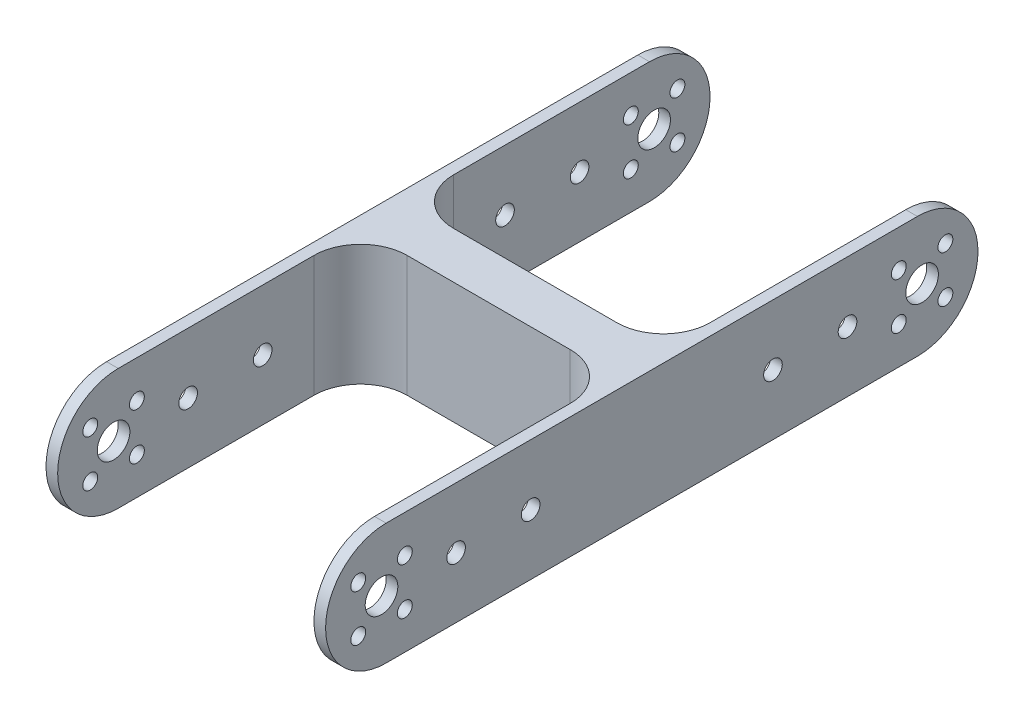
SolidWorks part; units mm, degrees
ref_plane "前视基准面" through (0, 0, 0) normal (0, 0, 1) x (1, 0, 0)
ref_plane "上视基准面" through (0, 0, 0) normal (0, 1, 0) x (1, 0, 0)
ref_plane "右视基准面" through (0, 0, 0) normal (1, 0, 0) x (0, 0, -1)
other "Configuration Table"
sketch "草图1" plane through (0, 0, 0) normal (0, 1, 0) x (1, 0, 0)
  line L0 (0, 0) -> (0, 140)
  line L1 (0, 140) -> (5, 140)
  line L2 (5, 140) -> (5, 85)
  line L3 (15, 75) -> (45, 75)
  line L4 (55, 85) -> (55, 140)
  line L5 (55, 140) -> (60, 140)
  line L6 (60, 140) -> (60, 0)
  line L7 (60, 0) -> (55, 0)
  line L8 (55, 0) -> (55, 55)
  line L9 (45, 65) -> (15, 65)
  line L10 (5, 55) -> (5, 0)
  line L11 (5, 0) -> (0, 0)
  arc A0 (55, 55) -> (45, 65) centre (45, 55) ccw
  arc A1 (5, 55) -> (15, 65) centre (15, 55) cw
  arc A2 (45, 75) -> (55, 85) centre (45, 85) ccw
  arc A3 (15, 75) -> (5, 85) centre (15, 85) cw
  point P3 (2.5, 140)
  point P16 (55, 65)
  point P19 (5, 65)
  point P22 (55, 75)
  point P25 (5, 75)
  dimension "D10" = 10
  dimension "D1" = 140
  dimension "D2" = 140
  dimension "D3" = 5
  dimension "D4" = 5
  dimension "D5" = 50
  dimension "D6" = 50
  dimension "D7" = 5
  dimension "D8" = 10
  dimension "D9" = 65
extrude "凸台-拉伸1" add sketch "草图1" along normal blind 26
sketch "草图2" plane through (60, 0, 0) normal (1, 0, 0) x (0, 0, -1)
  line L0 (-1000, 13) -> (49000, 13) construction
  line L1 (0, 26) -> (0, 0) construction
  line L2 (70, -974) -> (70, 49026) construction
  line L3 (0, 26) -> (140, 26) construction
  line L4 (0, 13) -> (12, 13)
  line L5 (12, 13) -> (28, 13)
  line L6 (7, 8) -> (17, 8)
  line L7 (7, 8) -> (7, 18)
  line L8 (7, 18) -> (17, 18)
  line L9 (17, 8) -> (17, 18)
  line L10 (7, 8) -> (17, 18) construction
  line L11 (7, 18) -> (17, 8) construction
  line L12 (28, 13) -> (44, 13)
  circle A0 centre (12, 13) radius 3.5
  circle A1 centre (7, 18) radius 1.6
  circle A2 centre (17, 18) radius 1.6
  circle A3 centre (17, 8) radius 1.6
  circle A4 centre (7, 8) radius 1.6
  circle A5 centre (28, 13) radius 2
  circle A6 centre (44, 13) radius 2
  circle A7 centre (96, 13) radius 2
  circle A8 centre (112, 13) radius 2
  circle A9 centre (123, 18) radius 1.6
  circle A10 centre (133, 18) radius 1.6
  circle A11 centre (133, 8) radius 1.6
  circle A12 centre (128, 13) radius 3.5
  circle A13 centre (123, 8) radius 1.6
  point P5 (0, 13)
  point P10 (70, 26)
  dimension "D2" = 7
  dimension "D5" = 3.2
  dimension "D8" = 4
  dimension "D10" = 4
  dimension "D1" = 12
  dimension "D3" = 10
  dimension "D4" = 10
  dimension "D7" = 16
  dimension "D9" = 16
  dimension "D6" = 4
extrude "切除-拉伸2" cut sketch "草图2" against normal through all contours A12 | A9 | A10 | A11 | A13 | A0 | A1 | A4 | A3 | A2 | A5 | A6 | A7 | A8 region at (60, 18, -123) region at (60, 18, -133) region at (60, 8, -133) region at (60, 13, -128) region at (60, 8, -123)
sketch "草图3" plane through (0, 0, 0) normal (-1, 0, 0) x (0, 0, 1)
  line L0 (-128, 13) -> (-127, 13)
  line L1 (-70, -974) -> (-70, 49026) construction
  line L2 (-140, 26) -> (-127, 26)
  line L3 (-140, 26) -> (-140, 0)
  line L4 (-140, 0) -> (-127, 0)
  line L5 (-127, 26) -> (-127, 0)
  line L6 (-140, 26) -> (0, 26) construction
  line L7 (0, 26) -> (-13, 26)
  line L8 (0, 26) -> (0, 0)
  line L9 (0, 0) -> (-13, 0)
  line L10 (-13, 26) -> (-13, 0)
  circle A2 centre (-127, 13) radius 13
  circle A3 centre (-13, 13) radius 13
  point P14 (-70, 26)
  line M8 (-140, 0) -> (0, 0)
  line M9 (0, 0) -> (0, 26)
  line M10 (0, 26) -> (-140, 26)
  line M11 (-140, 26) -> (-140, 0)
  dimension "D1" = 1
extrude "切除-拉伸5" cut sketch "草图3" against normal through all contours A2 M10 M11 | A2 L3 M8 | A3 M9 M8 | A3 L8 M10 region at (0, 23.0962, -137.0962) region at (0, 2.9038, -137.0962) region at (0, 23.0962, -2.9038) region at (0, 2.9038, -2.9038)
sketch "草图5" plane through (55, 0, 0) normal (-1, 0, 0) x (0, 0, 1)
  circle A0 centre (-128, 13) radius 10.5
  dimension "D1" = 21
extrude "切除-拉伸6" cut sketch "草图5" against normal blind 1.6
sketch "草图6" plane through (5, 0, 0) normal (1, 0, 0) x (0, 0, -1)
  circle A0 centre (128, 13) radius 10.5
  dimension "D1" = 21
extrude "切除-拉伸7" cut sketch "草图6" against normal blind 1.6
sketch "草图7" plane through (55, 0, 0) normal (-1, 0, 0) x (0, 0, 1)
  circle A0 centre (-12, 13) radius 10.5
  dimension "D1" = 21
extrude "切除-拉伸8" cut sketch "草图7" against normal blind 1.6
sketch "草图8" plane through (5, 0, 0) normal (1, 0, 0) x (0, 0, -1)
  circle A0 centre (12, 13) radius 10.5
  dimension "D1" = 21
extrude "切除-拉伸9" cut sketch "草图8" against normal blind 1.6
sketch "草图9" plane through (0, 26, 0) normal (0, 1, 0) x (1, 0, 0)
  line L0 (30, -925) -> (30, 49075) construction
  line L1 (45, 75) -> (15, 75) construction
  line L2 (30, 75) -> (30, 65)
  line L3 (15, 65) -> (45, 65) construction
  line L4 (60, 140) -> (55, 140) construction
  line L5 (2.5, 0) -> (57.5, 0)
  line L6 (2.5, 0) -> (2.5, 140)
  line L7 (2.5, 140) -> (57.5, 140)
  line L8 (57.5, 0) -> (57.5, 140)
  line L9 (2.5, 0) -> (57.5, 140) construction
  line L10 (2.5, 140) -> (57.5, 0) construction
  line L11 (2.5, 85.2059) -> (57.5, 85.2059)
  line L12 (-997.5, 70) -> (49002.5, 70) construction
  line L13 (2.5, 54.7941) -> (57.5, 54.7941)
  point P5 (30, 75)
  point P9 (30, 70)
  point P21 (2.5, 70)
extrude "切除-拉伸11" cut sketch "草图9" against normal through all contours L6 L11 L8 L9 | L8 L11 L3 L2 L7 L6 L9 | L3 L11 L8 L2 | L13 L6 L5 L8 | L13 L6 | L13 L8 region at (25.0549, 26, -114.8249) region at (50.3246, 26, -103.4706) region at (34.9451, 26, -25.1751) region at (9.6754, 26, -36.5294)
sketch "草图11" plane through (0, 26, 0) normal (0, 1, 0) x (1, 0, 0)
  line L1 (2.5, 85.2059) -> (57.5, 85.2059)
  line L2 (2.5, 85.2059) -> (2.5, 54.7941)
  line L3 (2.5, 54.7941) -> (57.5, 54.7941)
  line L4 (57.5, 85.2059) -> (57.5, 54.7941)
extrude "切除-拉伸12" cut sketch "草图11" against normal through all
sketch "草图12" plane through (0, 26, 0) normal (0, 1, 0) x (1, 0, 0)
  line L0 (-997.5, 70) -> (49002.5, 70) construction
  line L1 (2.5, 13) -> (2.5, 127) construction
  line L2 (2.5, 70) -> (2.5, 75)
  line L3 (57.5, 13) -> (57.5, 127) construction
  line L4 (2.5, 75) -> (57.5, 75)
  line L5 (2.5, 75) -> (2.5, 65)
  line L6 (2.5, 65) -> (57.5, 65)
  line L7 (57.5, 75) -> (57.5, 65)
  line L8 (2.5, 75) -> (12.5, 75)
  line L9 (30, -935) -> (30, 49065) construction
  line L10 (2.5, 75) -> (2.5, 85)
  line L11 (2.5, 65) -> (2.5, 55)
  line L12 (57.5, 65) -> (57.5, 55)
  line L13 (57.5, 75) -> (57.5, 85)
  arc A0 (2.5, 85) -> (12.5, 75) centre (12.5, 85) ccw
  arc A1 (57.5, 85) -> (47.5, 75) centre (47.5, 85) cw
  arc A2 (57.5, 55) -> (47.5, 65) centre (47.5, 55) ccw
  arc A3 (2.5, 55) -> (12.5, 65) centre (12.5, 55) cw
  point P5 (2.5, 70)
  point P16 (30, 65)
  line M6 (2.5, 13) -> (2.5, 127)
  dimension "D1" = 5
  dimension "D2" = 10
  dimension "D3" = 10
  dimension "D4" = 10
extrude "凸台-拉伸2" add sketch "草图12" against normal blind 26 contours A0 L4 M6 | L7 L4 L6 M6 | A3 L6 M6 | A2 L12 L6 | L13 A1 L4 region at (30, 26, -70) region at (4.7337, 26, -77.2337) region at (4.7337, 26, -62.7663) region at (55.2663, 26, -77.2337) region at (55.2663, 26, -62.7663)
sketch "草图13" plane through (0, 0, 0) normal (0, -1, 0) x (1, 0, 0)
  line L0 (60, -13) -> (60, -127) construction
  line L1 (0, 0) -> (60, 0)
  line L2 (0, 0) -> (0, -70)
  line L3 (0, -70) -> (60, -70)
  line L4 (60, 0) -> (60, -70)
